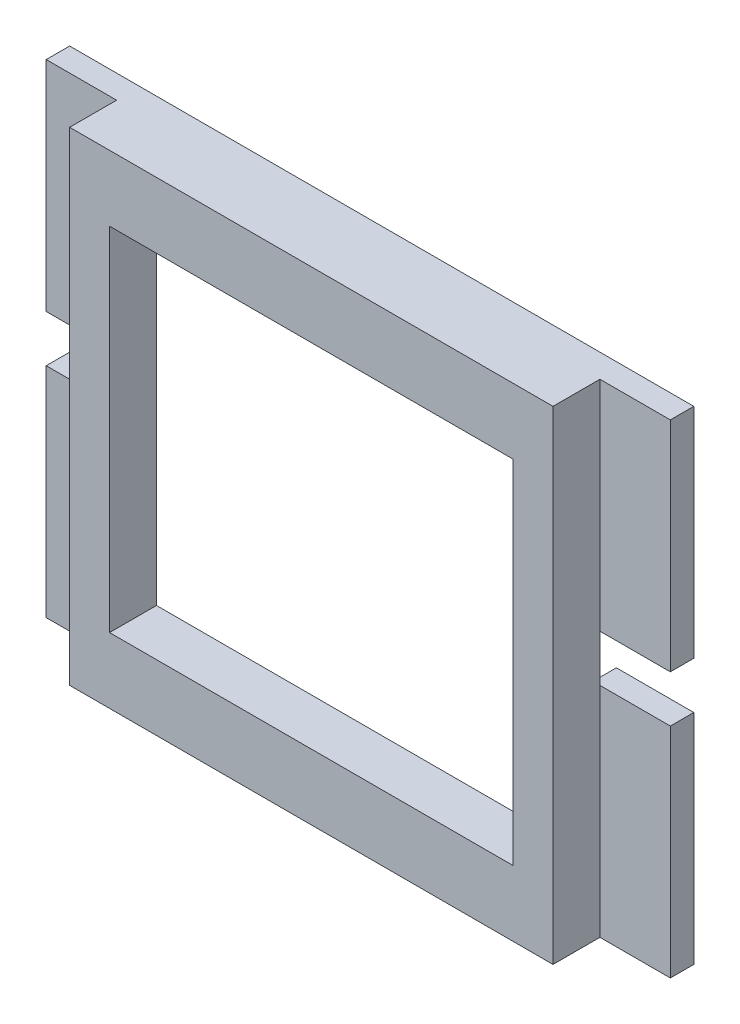
SolidWorks part; units mm, degrees
ref_plane "Front Plane" through (0, 0, 0) normal (0, 0, 1) x (1, 0, 0)
ref_plane "Top Plane" through (0, 0, 0) normal (0, 1, 0) x (1, 0, 0)
ref_plane "Right Plane" through (0, 0, 0) normal (1, 0, 0) x (0, 0, -1)
sketch "Sketch1" plane through (0, 0, 0) normal (0, 0, 1) x (1, 0, 0)
  line L1 (0, 0) -> (103, 0)
  line L2 (0, 0) -> (0, -103)
  line L3 (0, -103) -> (103, -103)
  line L4 (103, 0) -> (103, -103)
  dimension "D1" = 103
  dimension "D2" = 103
extrude "Boss-Extrude1" add sketch "Sketch1" along normal blind 15
sketch "Sketch3" plane through (0, 0, 0) normal (0, 0, -1) x (-1, 0, 0)
  line L0 (-51.5, 0) -> (-51.5, -103) construction
  line L1 (0, 0) -> (15, 0)
  line L2 (0, 0) -> (0, -103)
  line L3 (0, -103) -> (15, -103)
  line L4 (15, 0) -> (15, -103)
  line L5 (-103, 0) -> (0, 0) construction
  line L6 (0, -103) -> (-103, -103) construction
  line L7 (-103, -103) -> (-118, -103)
  line L8 (-118, 0) -> (-118, -103)
  line L9 (-103, 0) -> (-118, 0)
  line L10 (-103, 0) -> (-103, -103)
  dimension "D1" = 15
extrude "Boss-Extrude2" add sketch "Sketch3" against normal blind 5
sketch "Sketch4" plane through (0, 0, 0) normal (0, 0, -1) x (-1, 0, 0)
  line L0 (-103, 0) -> (0, -103)
  line L1 (0, 0) -> (-103, -103)
  line L3 (-101.5, -101.5) -> (-1.5, -101.5)
  line L4 (-101.5, -101.5) -> (-101.5, -1.5)
  line L5 (-101.5, -1.5) -> (-1.5, -1.5)
  line L6 (-1.5, -101.5) -> (-1.5, -1.5)
  line L7 (-101.5, -101.5) -> (-1.5, -1.5) construction
  line L8 (-101.5, -1.5) -> (-1.5, -101.5) construction
  point P8 (-51.5, -51.5)
  dimension "D1" = 100
extrude "Cut-Extrude1" cut sketch "Sketch4" against normal blind 5 contours L4 L1 L0 | L5 L0 L1 | L0 L6 L1 | L1 L3 L0 region at (51.5, -18.1667, 0) region at (84.8333, -51.5, 0) region at (18.1667, -51.5, 0) region at (51.5, -84.8333, 0)
sketch "Sketch5" plane through (0, 0, 5) normal (0, 0, -1) x (-1, 0, 0)
  line L1 (-94.5, -89) -> (-8.5, -89)
  line L2 (-94.5, -89) -> (-94.5, -14)
  line L3 (-94.5, -14) -> (-8.5, -14)
  line L4 (-8.5, -89) -> (-8.5, -14)
  line L5 (-94.5, -89) -> (-8.5, -14) construction
  line L6 (-94.5, -14) -> (-8.5, -89) construction
  point P0 (-51.5, -51.5)
  point P5 (0, 0)
  point P6 (0, 0)
  dimension "D1" = 86
  dimension "D2" = 75
extrude "Cut-Extrude2" cut sketch "Sketch5" against normal through all
sketch "Sketch6" plane through (0, -101.5, 0) normal (0, 1, 0) x (1, 0, 0)
  line L0 (101.5, 0) -> (1.5, 0) construction
  line L1 (46.5, 5) -> (56.5, 5)
  line L2 (46.5, 5) -> (46.5, -5)
  line L3 (46.5, -5) -> (56.5, -5)
  line L4 (56.5, 5) -> (56.5, -5)
  line L5 (46.5, 5) -> (56.5, -5) construction
  line L6 (46.5, -5) -> (56.5, 5) construction
  line L7 (101.5, -5) -> (1.5, -5) construction
  point P0 (51.5, 0)
  dimension "D1" = 10
sketch "Sketch7" plane through (0, -89, 0) normal (0, 1, 0) x (1, 0, 0)
  line L0 (94.5, -15) -> (94.5, -5) construction
  line L1 (8.5, -5) -> (94.5, -5)
  line L2 (8.5, -5) -> (8.5, -21.889)
  line L3 (8.5, -21.889) -> (94.5, -21.889)
  line L4 (94.5, -5) -> (94.5, -21.889)
  dimension "D1" = 16.889
sketch "Sketch9" plane through (-15, 0, 0) normal (-1, 0, 0) x (0, 0, 1)
  line L0 (0, -103) -> (0, 0) construction
  line L1 (5, -56.5) -> (-5, -56.5)
  line L2 (5, -56.5) -> (5, -46.5)
  line L3 (5, -46.5) -> (-5, -46.5)
  line L4 (-5, -56.5) -> (-5, -46.5)
  line L5 (5, -56.5) -> (-5, -46.5) construction
  line L6 (5, -46.5) -> (-5, -56.5) construction
  line L7 (5, -103) -> (5, 0) construction
  point P0 (0, -51.5)
  point P7 (5, -46.4607)
extrude "Cut-Extrude5" cut sketch "Sketch9" against normal up to surface (23.5 mm away) up to face at (8.5, -51.5, 10)
ref_axis "Axis1" through (51.5, -101.5, 0) along (0, 1, 0)
ref_plane "Plane4" through (51.5, 0, 0) normal (-1, 0, 0) x (0, 1, 0)
mirror "Mirror1" about plane through (51.5, 0, 0) normal (-1, 0, 0) of "Cut-Extrude5"
